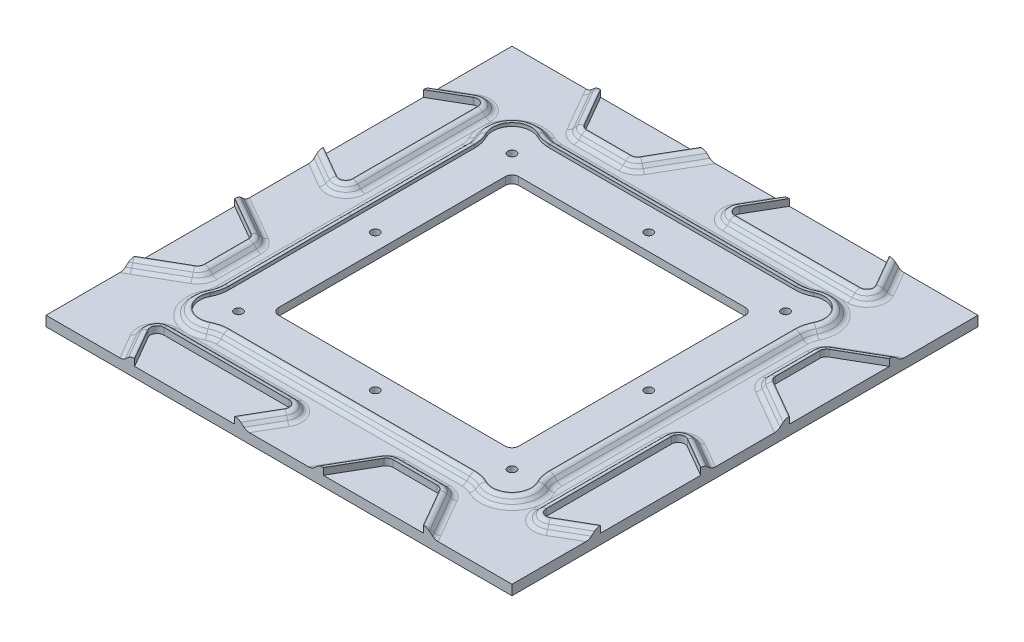
SolidWorks part; units mm, degrees
material "6061 Alloy"
ref_plane "Front Plane" through (0, 0, 0) normal (0, 0, 1) x (1, 0, 0)
ref_plane "Top Plane" through (0, 0, 0) normal (0, 1, 0) x (1, 0, 0)
ref_plane "Right Plane" through (0, 0, 0) normal (1, 0, 0) x (0, 0, -1)
sketch "Sketch1" plane through (0, 0, 0) normal (0, 1, 0) x (1, 0, 0)
  line L1 (-69.85, -69.85) -> (69.85, -69.85)
  line L2 (-69.85, -69.85) -> (-69.85, 69.85)
  line L3 (-69.85, 69.85) -> (69.85, 69.85)
  line L4 (69.85, -69.85) -> (69.85, 69.85)
  line L5 (-69.85, -69.85) -> (69.85, 69.85) construction
  line L6 (-69.85, 69.85) -> (69.85, -69.85) construction
  point P0 (0, 0)
  dimension "D1" = 139.7
extrude "Boss-Extrude1" add sketch "Sketch1" along normal mid plane 3
ref_axis "Axis1" through (0, 22.8445, 0) along (0, -1, 0)
sketch "Sketch2" plane through (0, 1.5, 0) normal (0, 1, 0) x (1, 0, 0)
  line L0 (-69.85, -69.85) -> (-43.2833, -69.85) construction
  line L1 (-47.0361, -57.35) -> (-50.5002, -57.35) construction
  line L3 (-69.85, -69.85) -> (69.85, -69.85) construction
  line L5 (-43.2833, -69.85) -> (-13.2833, -69.85) construction
  line L12 (-13.2833, -69.85) -> (13.2833, -69.85) construction
  line L13 (13.2833, -69.85) -> (43.2833, -69.85) construction
  line L14 (43.2833, -69.85) -> (69.85, -69.85) construction
  line L15 (-43.2833, -69.85) -> (-48.7682, -60.35)
  line L16 (-47.0361, -57.35) -> (-9.5306, -57.35)
  line L17 (-13.2833, -69.85) -> (-7.7985, -60.35)
  line L18 (-50.5002, -57.35) -> (-48.7682, -60.35) construction
  line L19 (-9.5306, -57.35) -> (-6.0665, -57.35) construction
  line L20 (-6.0665, -57.35) -> (-7.7985, -60.35) construction
  arc A0 (-48.7682, -60.35) -> (-47.0361, -57.35) centre (-47.0361, -59.35) cw
  arc A1 (-9.5306, -57.35) -> (-7.7985, -60.35) centre (-9.5306, -59.35) cw
  dimension "D3" = 2
  dimension "D1" = 30
  dimension "D2" = 60
  dimension "D4" = 12.5
ref_plane "Plane1" through (-43.2833, 1.5, 69.85) normal (-0.5, 0, -0.866) x (-0.866, 0, 0.5)
sketch "Sketch3" plane through (-43.2833, 1.5, 69.85) normal (-0.5, 0, -0.866) x (-0.866, 0, 0.5)
  line L0 (0, 0) -> (3, 0)
  line L1 (3, 0) -> (1, 2)
  line L2 (1, 2) -> (0, 2)
  line L3 (0, 2) -> (0, 0)
  point P3 (2.0227, 2)
  dimension "D1" = 2
  dimension "D2" = 3
  dimension "D3" = 45
sweep "Sweep1" add profiles "Sketch3" path "Sketch2"
sketch "Sketch4" plane through (0, 1.5, 0) normal (0, 1, 0) x (1, 0, 0)
  line L0 (13.2833, -69.85) -> (43.2833, -69.85) construction
  line L1 (13.2833, -69.85) -> (43.2833, -69.85) construction
  line L3 (13.2833, -69.85) -> (19.9229, -58.35)
  line L4 (21.6549, -57.35) -> (34.9118, -57.35)
  line L5 (43.2833, -69.85) -> (36.6438, -58.35)
  line L6 (-47.0361, -57.35) -> (-9.5306, -57.35) construction
  line L7 (-13.2833, -69.85) -> (-7.7985, -60.35) construction
  line L8 (13.2833, -69.85) -> (7.5098, -79.85)
  line L9 (43.2833, -69.85) -> (49.0568, -79.85)
  arc A0 (19.9229, -58.35) -> (21.6549, -57.35) centre (21.6549, -59.35) cw
  arc A1 (34.9118, -57.35) -> (36.6438, -58.35) centre (34.9118, -59.35) cw
  arc A2 (-7.7985, -60.35) -> (-9.5306, -57.35) centre (-9.5306, -59.35) ccw construction
  point P8 (0, 0)
  dimension "D1" = 10
ref_plane "Plane2" through (13.2833, 1.5, 69.85) normal (0.5, 0, -0.866) x (-0.866, 0, -0.5)
sketch "Sketch5" plane through (13.2833, 1.5, 69.85) normal (0.5, 0, -0.866) x (-0.866, 0, -0.5)
  line L0 (0, 0) -> (3, 0)
  line L1 (3, 0) -> (1, 2)
  line L2 (1, 2) -> (0, 2)
  line L3 (0, 2) -> (0, 0)
  dimension "D1" = 2
  dimension "D2" = 3
  dimension "D3" = 45
sweep "Sweep2" add profiles "Sketch5" path "Sketch4"
pattern_circular "CirPattern1" count 4 over 360 about axis through (0, 22.8445, 0) along (0, -1, 0) of "Sweep2", "Sweep1"
sketch "Sketch6" plane through (0, 1.5, 0) normal (0, 1, 0) x (1, 0, 0)
  line L0 (-48, 36.848) -> (-48, -36.848)
  line L1 (-48, -48) -> (48, -48) construction
  line L2 (-48, -48) -> (-48, 48) construction
  line L3 (-48, 48) -> (48, 48) construction
  line L4 (48, -48) -> (48, 48) construction
  line L5 (-48, -48) -> (48, 48) construction
  line L6 (-48, 48) -> (48, -48) construction
  line L7 (-36.848, -48) -> (36.848, -48)
  line L8 (36.848, 48) -> (-36.848, 48)
  line L9 (48, 36.848) -> (48, -36.848)
  arc A0 (-48, 39.8683) -> (-39.8683, 48) centre (-43.9341, 43.9341) cw construction
  arc A1 (39.8683, 48) -> (48, 39.8683) centre (43.9341, 43.9341) cw construction
  arc A2 (-48, -39.8683) -> (-39.8683, -48) centre (-43.9341, -43.9341) ccw construction
  arc A3 (48, -39.8683) -> (39.8683, -48) centre (43.9341, -43.9341) cw construction
  arc A4 (-41.3471, 49.0693) -> (-49.0693, 41.3471) centre (-43.9341, 43.9341) ccw
  arc A5 (-41.3471, 49.0693) -> (-36.848, 48) centre (-36.848, 58) ccw
  arc A6 (-49.0693, 41.3471) -> (-48, 36.848) centre (-58, 36.848) cw
  arc A7 (41.3471, 49.0693) -> (36.848, 48) centre (36.848, 58) cw
  arc A8 (49.0693, 41.3471) -> (41.3471, 49.0693) centre (43.9341, 43.9341) ccw
  arc A9 (49.0693, 41.3471) -> (48, 36.848) centre (58, 36.848) ccw
  arc A10 (49.0693, -41.3471) -> (48, -36.848) centre (58, -36.848) cw
  arc A11 (41.3471, -49.0693) -> (49.0693, -41.3471) centre (43.9341, -43.9341) ccw
  arc A12 (41.3471, -49.0693) -> (36.848, -48) centre (36.848, -58) ccw
  arc A13 (-41.3471, -49.0693) -> (-36.848, -48) centre (-36.848, -58) cw
  arc A14 (-49.0693, -41.3471) -> (-41.3471, -49.0693) centre (-43.9341, -43.9341) ccw
  arc A15 (-49.0693, -41.3471) -> (-48, -36.848) centre (-58, -36.848) ccw
  point P0 (0, 0)
  point P48 (0, 0)
  dimension "D2" = 5.75
  dimension "D3" = 10
  dimension "D1" = 96
  dimension "D4" = 4
sketch "Sketch7" plane through (0, 0, 0) normal (0, 0, 1) x (1, 0, 0)
  line L0 (-48, 1.5) -> (-51, 1.5)
  line L1 (-51, 1.5) -> (-49, 3.5)
  line L2 (-49, 3.5) -> (-48, 3.5)
  line L3 (-48, 3.5) -> (-48, 1.5)
  point P0 (-48, 1.5)
  point P4 (-49.7237, 4.25)
  dimension "D1" = 2
  dimension "D2" = 3
  dimension "D3" = 45
sweep "Sweep3" add profiles "Sketch7" path "Sketch6"
sketch "Sketch8" plane through (0, 1.5, 0) normal (0, 1, 0) x (1, 0, 0)
  line L1 (-69.85, 69.85) -> (69.85, 69.85)
  line L2 (-69.85, 69.85) -> (-69.85, -69.85)
  line L3 (-69.85, -69.85) -> (69.85, -69.85)
  line L4 (69.85, 69.85) -> (69.85, -69.85)
  line L5 (-69.85, 69.85) -> (69.85, -69.85) construction
  line L6 (-69.85, -69.85) -> (69.85, 69.85) construction
  line L7 (-100, 100) -> (100, 100)
  line L8 (-100, 100) -> (-100, -100)
  line L9 (-100, -100) -> (100, -100)
  line L10 (100, 100) -> (100, -100)
  line L11 (-100, 100) -> (100, -100) construction
  line L12 (-100, -100) -> (100, 100) construction
  point P0 (0, 0)
  point P7 (0, 0)
  dimension "D1" = 200
extrude "Cut-Extrude1" cut sketch "Sketch8" against normal through all both and the other way through all
fillet "Fillet1" radius 2 122 edges at (-15.5927, 3.5, -63.85) (-20.1549, 3.5, -56.7519) (-44.2937, 3.5, -69.6) (-40.8296, 3.5, -63.6) (-36.4118, 3.5, -56.7519) (-13.572, 1.5, -63.35) (-19.1549, 1.5, -55.0199) (-46.3144, 1.5, -69.1) (-42.5616, 1.5, -62.6) (-37.4118, 1.5, -55.0199) (47.0361, 3.5, -65.35) (49.6342, 3.5, -57.85) (9.5306, 3.5, -65.35) (6.9325, 3.5, -57.85) (49.0568, 1.5, -65.85) (51.3662, 1.5, -56.85) (7.5098, 1.5, -65.85) (5.2004, 1.5, -56.85) (69.6, 3.5, -44.2937) (63.6, 3.5, -40.8296) (56.7519, 3.5, -36.4118) (56.35, 3.5, -28.2833) (56.7519, 3.5, -20.1549) (69.1, 1.5, -46.3144) (62.6, 1.5, -42.5616) (55.0199, 1.5, -37.4118) (54.35, 1.5, -28.2833) (55.0199, 1.5, -19.1549) (65.35, 3.5, 9.5306) (57.85, 3.5, 6.9325) (56.35, 3.5, 28.2833) (57.85, 3.5, 49.6342) (65.85, 1.5, 7.5098) (56.85, 1.5, 5.2004) (54.35, 1.5, 28.2833) (56.85, 1.5, 51.3662) (44.2937, 3.5, 69.6) (40.8296, 3.5, 63.6) (36.4118, 3.5, 56.7519) (28.2833, 3.5, 56.35) (20.1549, 3.5, 56.7519) (46.3144, 1.5, 69.1) (42.5616, 1.5, 62.6) (37.4118, 1.5, 55.0199) (28.2833, 1.5, 54.35) (19.1549, 1.5, 55.0199) (-9.5306, 3.5, 65.35) (-6.9325, 3.5, 57.85) (-28.2833, 3.5, 56.35) (-49.6342, 3.5, 57.85) (-49.0568, 1.5, 65.85) (-7.5098, 1.5, 65.85) (-5.2004, 1.5, 56.85) (-28.2833, 1.5, 54.35) (-38.929, 3.5, 49.2439) (0, 3.5, 49) (38.929, 3.5, 49.2439) (48.7071, 3.5, 48.7071) (49.2439, 3.5, 38.929) (49, 3.5, 0) (49.2439, 3.5, -38.929) (48.7071, 3.5, -48.7071) (38.929, 3.5, -49.2439) (0, 3.5, -49) (-38.929, 3.5, -49.2439) (-48.7071, 3.5, -48.7071) (-49.2439, 3.5, -38.929) (-49, 3.5, -18.424) (-49, 3.5, 18.424) (-49.2439, 3.5, 38.929) (-38.4665, 1.5, 51.1897) (0, 1.5, 51) (38.4665, 1.5, 51.1897) (50.1213, 1.5, 50.1213) (51.1897, 1.5, 38.4665) (51, 1.5, 0) (51.1897, 1.5, -38.4665) (50.1213, 1.5, -50.1213) (38.4665, 1.5, -51.1897) (0, 1.5, -51) (-38.4665, 1.5, -51.1897) (-50.1213, 1.5, -50.1213) (-51.1897, 1.5, -38.4665) (-51, 1.5, -18.424) (-51, 1.5, 18.424) (-51.1897, 1.5, 38.4665) (-63.85, 3.5, 15.5927) (-56.7519, 3.5, 20.1549) (-56.35, 3.5, 28.2833) (-56.7519, 3.5, 36.4118) (-69.6, 3.5, 44.2937) (-63.35, 1.5, 13.572) (-55.0199, 1.5, 19.1549) (-54.35, 1.5, 28.2833) (-55.0199, 1.5, 37.4118) (-69.1, 1.5, 46.3144) (-65.35, 3.5, -47.0361) (-57.85, 3.5, -49.6342) (-56.35, 3.5, -28.2833) (-57.85, 3.5, -6.9325) (-65.85, 1.5, -49.0568) (-56.85, 1.5, -51.3662) (-54.35, 1.5, -28.2833) (-56.85, 1.5, -5.2004) (-28.2833, 3.5, -56.35) (-28.2833, 1.5, -54.35) (28.2833, 3.5, -56.35) (28.2833, 1.5, -54.35) (63.85, 3.5, -15.5927) (63.35, 1.5, -13.572) (65.35, 3.5, 47.0361) (65.85, 1.5, 49.0568) (15.5927, 3.5, 63.85) (13.572, 1.5, 63.35) (-47.0361, 3.5, 65.35) (-51.3662, 1.5, 56.85) (-48.7071, 3.5, 48.7071) (-50.1213, 1.5, 50.1213) (-63.6, 3.5, 40.8296) (-62.6, 1.5, 42.5616) (-65.35, 3.5, -9.5306) (-65.85, 1.5, -7.5098)
sketch "Sketch9" plane through (0, 1.5, 0) normal (0, 1, 0) x (1, 0, 0)
  line L5 (-48, 36.848) -> (-48, 0)
  line L6 (-48, 0) -> (-48, -36.848)
  line L7 (-36.848, -48) -> (36.848, -48)
  line L8 (48, -36.848) -> (48, 36.848)
  line L9 (36.848, 48) -> (-36.848, 48)
  line L10 (-48, 36.848) -> (-48, 0)
  line L11 (-48, 0) -> (-48, -36.848)
  line L12 (-36.848, -48) -> (36.848, -48)
  line L13 (48, -36.848) -> (48, 36.848)
  line L14 (36.848, 48) -> (-36.848, 48)
  arc A12 (-49.0693, -41.3471) -> (-48, -36.848) centre (-58, -36.848) ccw
  arc A13 (-49.0693, -41.3471) -> (-41.3471, -49.0693) centre (-43.9341, -43.9341) ccw
  arc A14 (-36.848, -48) -> (-41.3471, -49.0693) centre (-36.848, -58) ccw
  arc A15 (41.3471, -49.0693) -> (36.848, -48) centre (36.848, -58) ccw
  arc A16 (41.3471, -49.0693) -> (49.0693, -41.3471) centre (43.9341, -43.9341) ccw
  arc A17 (48, -36.848) -> (49.0693, -41.3471) centre (58, -36.848) ccw
  arc A18 (49.0693, 41.3471) -> (48, 36.848) centre (58, 36.848) ccw
  arc A19 (49.0693, 41.3471) -> (41.3471, 49.0693) centre (43.9341, 43.9341) ccw
  arc A20 (36.848, 48) -> (41.3471, 49.0693) centre (36.848, 58) ccw
  arc A21 (-41.3471, 49.0693) -> (-36.848, 48) centre (-36.848, 58) ccw
  arc A22 (-41.3471, 49.0693) -> (-49.0693, 41.3471) centre (-43.9341, 43.9341) ccw
  arc A23 (-48, 36.848) -> (-49.0693, 41.3471) centre (-58, 36.848) ccw
  arc A24 (-49.0693, -41.3471) -> (-48, -36.848) centre (-58, -36.848) ccw
  arc A25 (-49.0693, -41.3471) -> (-41.3471, -49.0693) centre (-43.9341, -43.9341) ccw
  arc A26 (-36.848, -48) -> (-41.3471, -49.0693) centre (-36.848, -58) ccw
  arc A27 (41.3471, -49.0693) -> (36.848, -48) centre (36.848, -58) ccw
  arc A28 (41.3471, -49.0693) -> (49.0693, -41.3471) centre (43.9341, -43.9341) ccw
  arc A29 (48, -36.848) -> (49.0693, -41.3471) centre (58, -36.848) ccw
  arc A30 (49.0693, 41.3471) -> (48, 36.848) centre (58, 36.848) ccw
  arc A31 (49.0693, 41.3471) -> (41.3471, 49.0693) centre (43.9341, 43.9341) ccw
  arc A32 (36.848, 48) -> (41.3471, 49.0693) centre (36.848, 58) ccw
  arc A33 (-41.3471, 49.0693) -> (-36.848, 48) centre (-36.848, 58) ccw
  arc A34 (-41.3471, 49.0693) -> (-49.0693, 41.3471) centre (-43.9341, 43.9341) ccw
  arc A35 (-48, 36.848) -> (-49.0693, 41.3471) centre (-58, 36.848) ccw
  dimension "D1" = 0
extrude "Boss-Extrude2" add sketch "Sketch9" along normal blind 1
sketch "Sketch10" plane through (0, -1.5, 0) normal (0, -1, 0) x (1, 0, 0)
  line L0 (-36.848, 48.1716) -> (36.848, 48.1716) construction
  line L1 (-46, -46) -> (46, -46)
  line L2 (-46, -46) -> (-46, 46)
  line L3 (-46, 46) -> (46, 46)
  line L4 (46, -46) -> (46, 46)
  line L5 (-46, -46) -> (46, 46) construction
  line L6 (-46, 46) -> (46, -46) construction
  point P0 (0, 0)
  dimension "D1" = 92
  dimension "D2" = 2.1716
extrude "Cut-Extrude2" cut sketch "Sketch10" against normal offset from surface (1.7 mm away) 2.3 up to face at (-2.8235, 2.5, 0)
sketch "Sketch11" plane through (0, 0.2, 0) normal (0, -1, 0) x (1, 0, 0)
  line L0 (46, -46) -> (46, 46) construction
  line L1 (-36, -36) -> (36, -36)
  line L2 (-36, -36) -> (-36, 36)
  line L3 (-36, 36) -> (36, 36)
  line L4 (36, -36) -> (36, 36)
  line L5 (-36, -36) -> (36, 36) construction
  line L6 (-36, 36) -> (36, -36) construction
  point P0 (0, 0)
  dimension "D1" = 10
  dimension "D2" = 72
extrude "Cut-Extrude3" cut sketch "Sketch11" against normal through all both and the other way through all
fillet "Fillet2" radius 2 8 edges at (36, 1.35, -36) (-36, 1.35, -36) (36, 1.35, 36) (-36, 1.35, 36) (46, -0.65, -46) (-46, -0.65, -46) (46, -0.65, 46) (-46, -0.65, 46)
sketch "Sketch13" plane through (0, 0.2, 0) normal (0, -1, 0) x (1, 0, 0)
  line L0 (-46, 44) -> (-46, -44) construction
  line L2 (44, 46) -> (-44, 46) construction
  line L3 (46, -44) -> (46, 44) construction
  line L4 (-44, -46) -> (44, -46) construction
  point P0 (41, 41)
  point P1 (0, 41)
  point P2 (-41, 41)
  point P3 (-41, 0)
  point P4 (-41, -41)
  point P5 (0, -41)
  point P6 (41, -41)
  point P7 (41, 0)
  point P8 (0, 0)
  point P9 (0, 0)
  point P18 (5.641, -41)
  point P20 (0, 0)
  point P21 (0, 0)
  dimension "D1" = 5
  dimension "D2" = 5
  dimension "D3" = 5
  dimension "D4" = 5
hole_wizard "M3x0.5 Tapped Hole1" positions "3DSketch1" profile "Sketch14" tap size "M3x0.5" standard "ANSI Metric" end condition through all
sketch3d "3DSketch1"
  point P0 (-41, 0.2, 41)
  point P3 (0, 0.2, 41)
  point P6 (41, 0.2, 41)
  point P9 (41, 0.2, 0)
  point P12 (41, 0.2, -41)
  point P15 (0, 0.2, -41)
  point P18 (-41, 0.2, -41)
  point P21 (-41, 0.2, 0)
sketch "Sketch14" plane through (-41, 0.2, 41) normal (1, 0, 0) x (0, 0, -1)
  line L0 (0, 0) -> (0, 3.3)
  line L1 (0, 3.3) -> (1.25, 3.3)
  line L2 (1.25, 3.3) -> (1.25, 0)
  line L5 (1.25, 0) -> (0, 0)
  line L11 (0, -6.35) -> (0, 107.95) construction
  dimension "Thru Tap Drill Dia." = 2.5
  dimension "Thru Tap Drill Depth" = 3.3
cosmetic thread "Hole Thread1"
cosmetic thread "Hole Thread2"
cosmetic thread "Hole Thread3"
cosmetic thread "Hole Thread4"
cosmetic thread "Hole Thread5"
cosmetic thread "Hole Thread6"
cosmetic thread "Hole Thread7"
cosmetic thread "Hole Thread8"
equation "\"D2@Sketch13\"=\"D1@Sketch13\""
equation "\"D3@Sketch13\"=\"D1@Sketch13\""
equation "\"D4@Sketch13\"=\"D1@Sketch13\""
